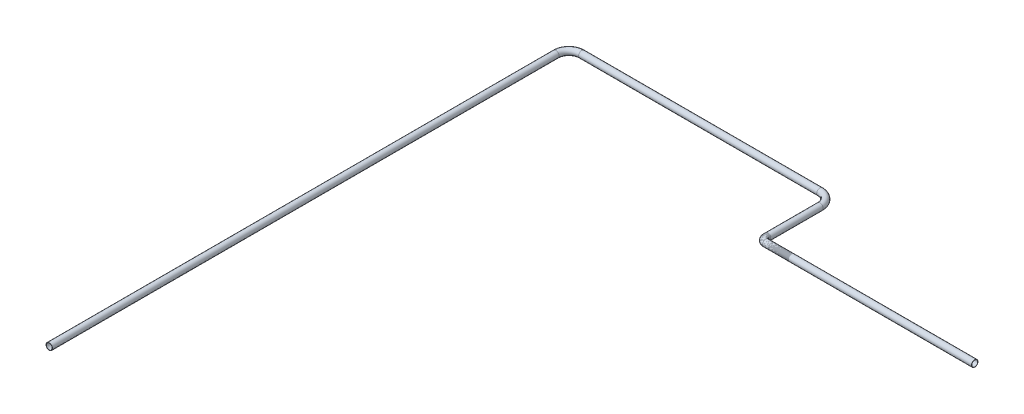
SolidWorks part; units mm, degrees
ref_plane "Front" through (0, 0, 0) normal (0, 0, 1) x (1, 0, 0)
ref_plane "Top" through (0, 0, 0) normal (0, 1, 0) x (1, 0, 0)
ref_plane "Right" through (0, 0, 0) normal (1, 0, 0) x (0, 0, -1)
sketch "Sketch13" plane through (0, 0, 0) normal (0, 1, 0) x (1, 0, 0)
  line L0 (-152.4, 0) -> (-2946.4, 0)
  line L1 (-3098.8, -152.4) -> (-3098.8, -6096)
  line L2 (0, -152.4) -> (0, -762)
  arc A0 (-3098.8, -152.4) -> (-2946.4, 0) centre (-2946.4, -152.4) cw
  arc A1 (0, -152.4) -> (-152.4, 0) centre (-152.4, -152.4) ccw
  point P7 (-3098.8, 0)
  point P10 (0, 0)
  dimension "D3" = 152.4
  dimension "D1" = 6096
  dimension "D2" = 762
  dimension "D4" = 2794
ref_plane "Plane1" through (0, 0, 762) normal (0, 0, 1) x (1, 0, 0)
sketch "Sketch14" plane through (0, 0, 762) normal (0, 0, 1) x (1, 0, 0)
  line L0 (0, 34.925) -> (0, 38.1) construction
  circle A0 centre (0, 0) radius 38.1
  circle A1 centre (0, 0) radius 34.925
  dimension "D1" = 76.2
  dimension "D2" = 3.175
sweep "Sweep1" add profiles "Sketch14" path "Sketch13"
sketch "Sketch15" plane through (0, 0, 0) normal (0, 1, 0) x (1, 0, 0)
  line L0 (0, -762) -> (0, -787.4)
  line L1 (-38.1, -762) -> (38.1, -762) construction
  line L2 (50.8, -838.2) -> (2501.9, -838.2)
  arc A0 (0, -787.4) -> (50.8, -838.2) centre (50.8, -787.4) ccw
  dimension "D1" = 50.8
  dimension "D2" = 25.4
  dimension "D3" = 2451.1
sketch "Sketch16" plane through (0, 0, 762) normal (0, 0, 1) x (1, 0, 0)
  circle A0 centre (0, 0) radius 34.925 construction
  circle A1 centre (0, 0) radius 38.1
  circle A2 centre (0, 0) radius 38.1
  circle A3 centre (0, 0) radius 34.925
  dimension "D1" = 0
sweep "Sweep2" add profiles "Sketch16" path "Sketch15"
sketch "Sketch17" plane through (0, 0, 0) normal (0, 1, 0) x (1, 0, 0)
  line L0 (0, -762) -> (0, -787.4)
  line L1 (-38.1, -762) -> (38.1, -762) construction
  line L2 (50.8, -838.2) -> (355.6, -838.2)
  arc A0 (0, -787.4) -> (50.8, -838.2) centre (50.8, -787.4) ccw
  dimension "D3" = 50.8
  dimension "D1" = 304.8
  dimension "D2" = 25.4
sketch "Sketch18" plane through (0, 0, 762) normal (0, 0, 1) x (1, 0, 0)
  circle A2 centre (0, 0) radius 38.1
  circle A3 centre (0, 0) radius 34.925
  point P1 (0, 0)
  point P3 (0, 0)
sweep "Sweep3" add profiles "Sketch18" path "Sketch17"
